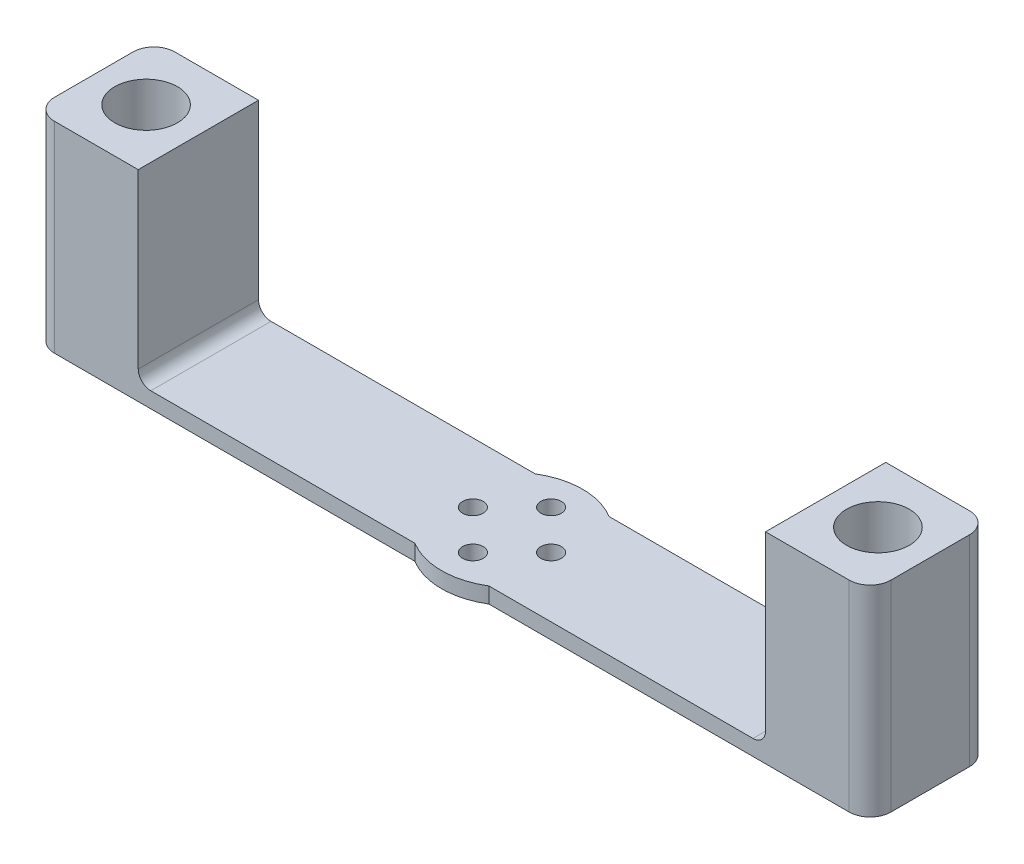
SolidWorks part; units mm, degrees
ref_plane "Front Plane" through (0, 0, 0) normal (0, 0, 1) x (1, 0, 0)
ref_plane "Top Plane" through (0, 0, 0) normal (0, 1, 0) x (1, 0, 0)
ref_plane "Right Plane" through (0, 0, 0) normal (1, 0, 0) x (0, 0, -1)
sketch "Sketch1" plane through (0, 0, 0) normal (0, 1, 0) x (1, 0, 0)
  line L0 (0, 0) -> (0, 4.9523) construction
  line L1 (0, 4.9523) -> (0, 0) construction
  line L2 (0, 0) -> (2.8355, 0) construction
  circle A0 centre (0, 0) radius 17.145
  circle A2 centre (0, 9.5) radius 2.5
  circle A3 centre (9.5, 0) radius 2.5
  circle A4 centre (0, -9.5) radius 2.5
  circle A5 centre (-9.5, 0) radius 2.5
  dimension "D2" = 34.29
  dimension "D3" = 5
extrude "Boss-Extrude1" add sketch "Sketch1" along normal blind 3.81
sketch "Sketch2" plane through (0, 3.81, 0) normal (0, 1, 0) x (1, 0, 0)
  line L1 (-96.52, -14.605) -> (96.52, -14.605)
  line L2 (-101.6, -9.525) -> (-101.6, 9.525)
  line L3 (-96.52, 14.605) -> (96.52, 14.605)
  line L4 (101.6, -9.525) -> (101.6, 9.525)
  line L5 (-101.6, -14.605) -> (101.6, 14.605) construction
  line L6 (-101.6, 14.605) -> (101.6, -14.605) construction
  circle A0 centre (-88.9, 0) radius 7.62
  circle A1 centre (88.9, 0) radius 7.62
  arc A3 (96.52, 14.605) -> (101.6, 9.525) centre (96.52, 9.525) cw
  arc A4 (96.52, -14.605) -> (101.6, -9.525) centre (96.52, -9.525) ccw
  arc A5 (-96.52, -14.605) -> (-101.6, -9.525) centre (-96.52, -9.525) cw
  arc A6 (-101.6, 9.525) -> (-96.52, 14.605) centre (-96.52, 9.525) cw
  circle A7 centre (9.5, 0) radius 2.5 construction
  circle A8 centre (0, 9.5) radius 2.5 construction
  circle A9 centre (-9.5, 0) radius 2.5 construction
  circle A10 centre (0, -9.5) radius 2.5 construction
  circle A11 centre (9.5, 0) radius 2.5
  circle A12 centre (0, 9.5) radius 2.5
  circle A13 centre (-9.5, 0) radius 2.5
  circle A14 centre (0, -9.5) radius 2.5
  point P0 (0, 0)
  dimension "D2" = 15.24
  dimension "D3" = 15.24
  dimension "D8" = 5.08
  dimension "D1" = 29.21
  dimension "D4" = 88.9
  dimension "D6" = 12.7
  dimension "D7" = 12.7
extrude "Boss-Extrude2" add sketch "Sketch2" along normal blind 45 and the other way through all
sketch "Sketch5" plane through (0, 0, -14.605) normal (0, 0, -1) x (-1, 0, 0)
  line L0 (-101.6, 0) -> (-101.6, 48.81)
  line L1 (-101.6, 48.81) -> (-76.2, 48.81)
  line L2 (-96.52, 48.81) -> (96.52, 48.81) construction
  line L3 (-76.2, 48.81) -> (-76.2, 3.81)
  line L4 (-76.2, 3.81) -> (76.2, 3.81)
  line L5 (0, 3.81) -> (0, 0)
  line L6 (101.6, 0) -> (-101.6, 0)
  line L7 (76.2, 48.81) -> (76.2, 3.81)
  line L8 (101.6, 48.81) -> (76.2, 48.81)
  line L9 (101.6, 0) -> (101.6, 48.81)
  line M8 (96.52, 48.81) -> (-96.52, 48.81)
  dimension "D1" = 25.4
  dimension "D2" = 3.81
extrude "Cut-Extrude2" cut sketch "Sketch5" against normal through all contours L7 L3 L4 M8 region at (0, 26.31, -14.605)
sketch "Sketch6" plane through (0, 0, 0) normal (0, -1, 0) x (1, 0, 0)
  circle A0 centre (-88.9, 0) radius 8.89
  circle A1 centre (-88.9, 0) radius 4.445
  circle A2 centre (88.9, 0) radius 8.89
  circle A3 centre (88.9, 0) radius 4.445
  dimension "D1" = 8.89
  dimension "D2" = 8.89
extrude "Boss-Extrude3" add sketch "Sketch6" against normal blind 4.572
fillet "Fillet2" radius 3.048 2 edges at (76.2, 3.81, 0) (-76.2, 3.81, 0)
